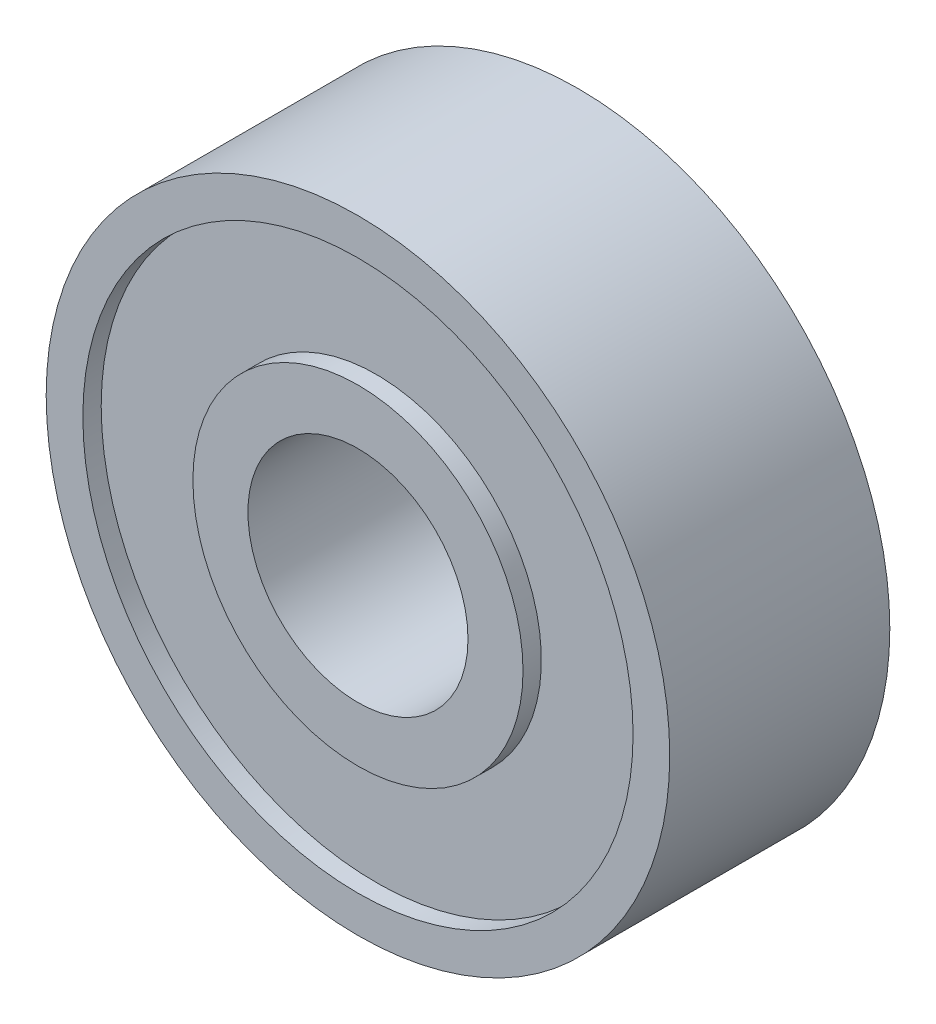
SolidWorks part; units mm, degrees
ref_plane "Front Plane" through (0, 0, 0) normal (0, 0, 1) x (1, 0, 0)
ref_plane "Top Plane" through (0, 0, 0) normal (0, 1, 0) x (1, 0, 0)
ref_plane "Right Plane" through (0, 0, 0) normal (1, 0, 0) x (0, 0, -1)
sketch "Sketch1" plane through (0, 0, 0) normal (0, 0, 1) x (1, 0, 0)
  circle A0 centre (0, 0) radius 8.5
  circle A1 centre (0, 0) radius 3
  dimension "D1" = 17
  dimension "D2" = 6
extrude "Boss-Extrude1" add sketch "Sketch1" along normal blind 6
sketch "Sketch2" plane through (0, 0, 0) normal (0, 1, 0) x (1, 0, 0)
  line L0 (8.5, 0) -> (-8.5, 0) construction
  line L1 (-4.5, -0.5) -> (-7.5, -0.5)
  line L2 (-4.5, -0.5) -> (-4.5, 0.5)
  line L3 (-4.5, 0.5) -> (-7.5, 0.5)
  line L4 (-7.5, -0.5) -> (-7.5, 0.5)
  line L5 (-4.5, -0.5) -> (-7.5, 0.5) construction
  line L6 (-4.5, 0.5) -> (-7.5, -0.5) construction
  line L7 (-8.5, 0) -> (-8.5, -6) construction
  line L8 (-8.5, -6) -> (8.5, -6) construction
  line L9 (0, 0) -> (0, -6) construction
  line L10 (-10.1745, -3) -> (9.9998, -3) construction
  line L11 (-4.5, -6.5) -> (-7.5, -6.5)
  line L12 (-7.5, -5.5) -> (-7.5, -6.5)
  line L13 (-4.5, -5.5) -> (-7.5, -5.5)
  line L14 (-4.5, -5.5) -> (-4.5, -6.5)
  point P0 (-6, 0)
  point P9 (-7.5, 0)
  dimension "D1" = 1
  dimension "D2" = 1
  dimension "D3" = 4.5
revolve "Cut-Revolve1" cut sketch "Sketch2" angle 360 about L9
